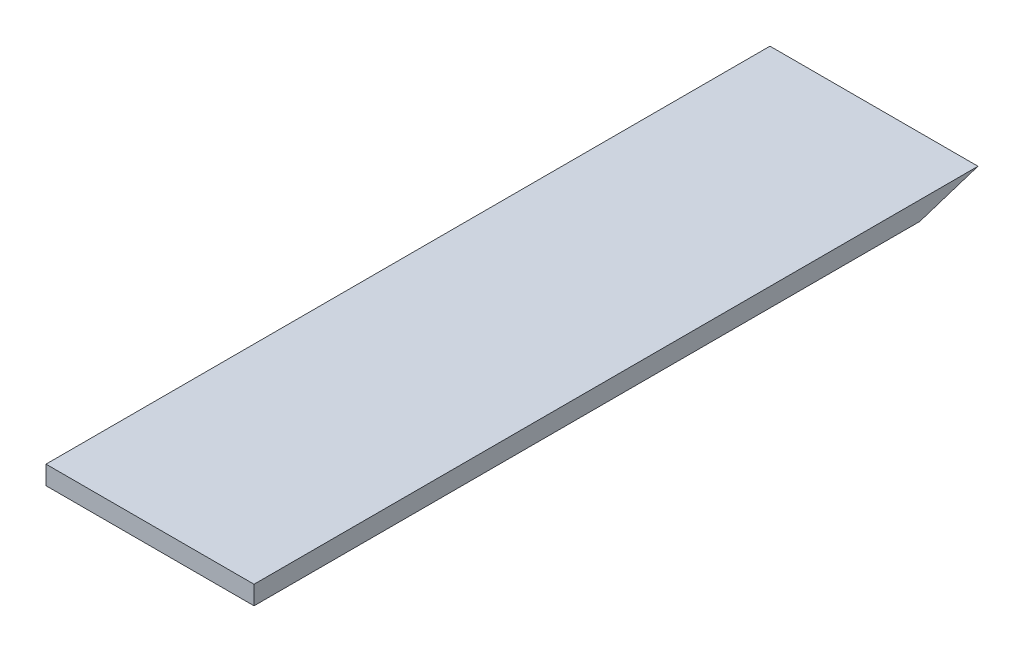
SolidWorks part; units mm, degrees
ref_plane "Front Plane" through (0, 0, 0) normal (0, 0, 1) x (1, 0, 0)
ref_plane "Top Plane" through (0, 0, 0) normal (0, 1, 0) x (1, 0, 0)
ref_plane "Right Plane" through (0, 0, 0) normal (1, 0, 0) x (0, 0, -1)
sketch "Sketch1" plane through (0, 0, 0) normal (1, 0, 0) x (0, 0, -1)
  line L19 (0, 9) -> (0, 0)
  line L20 (0, 0) -> (320, 0)
  line L21 (320, 0) -> (348, 9)
  line L37 (0, 9) -> (348, 9)
  dimension "D1" = 9
  dimension "D8" = 28
  dimension "D9" = 320
extrude "Boss-Extrude1" add sketch "Sketch1" along normal blind 100 contours L19 L20 L21 L37
